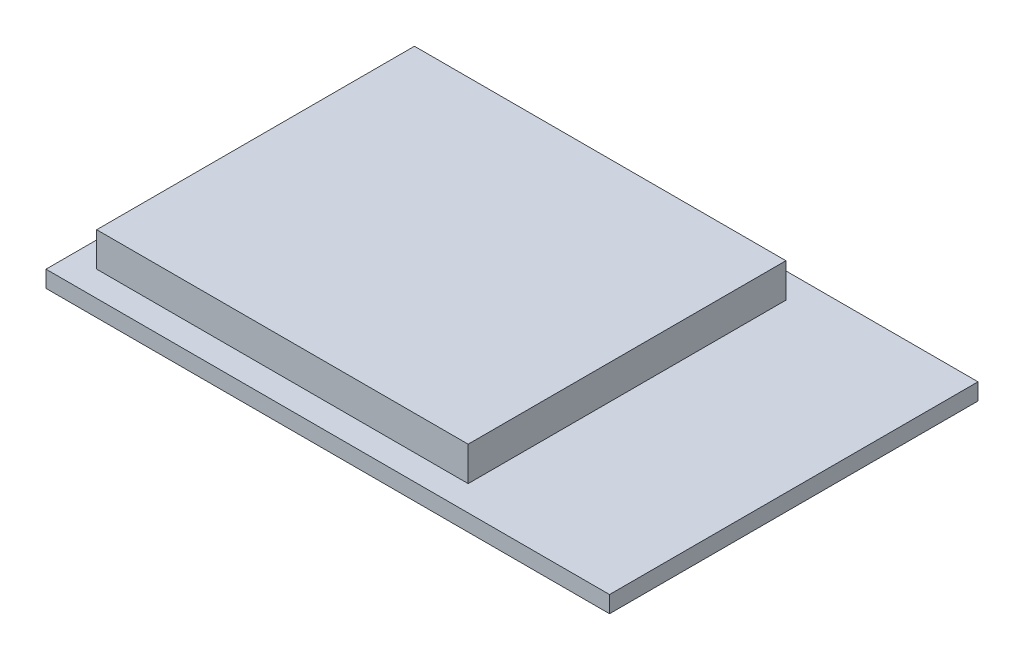
SolidWorks part; units mm, degrees
ref_plane "Ebene vorne" through (0, 0, 0) normal (0, 0, 1) x (1, 0, 0)
ref_plane "Ebene oben" through (0, 0, 0) normal (0, 1, 0) x (1, 0, 0)
ref_plane "Ebene rechts" through (0, 0, 0) normal (1, 0, 0) x (0, 0, -1)
sketch "Sketch1" plane through (0, 0, 0) normal (0, 1, 0) x (1, 0, 0)
  line L0 (-10.3687, 0) -> (25.2304, 0) construction
  line L2 (0, 11.05) -> (33.8, 11.05)
  line L3 (0, 11.05) -> (0, -11.05)
  line L4 (0, -11.05) -> (33.8, -11.05)
  line L5 (33.8, 11.05) -> (33.8, -11.05)
  dimension "D1" = 22.1
  dimension "D2" = 33.8
extrude "Boss-Extrude1" add sketch "Sketch1" along normal blind 1
sketch "Sketch2" plane through (0, 0, 0) normal (0, 1, 0) x (1, 0, 0)
  line L0 (0, 11.05) -> (0, -11.05) construction
  line L1 (23.8, 9.53) -> (1.52, 9.53)
  line L2 (23.8, 9.53) -> (23.8, -9.53)
  line L3 (23.8, -9.53) -> (1.52, -9.53)
  line L4 (1.52, 9.53) -> (1.52, -9.53)
  line L5 (0, -11.05) -> (33.8, -11.05) construction
  line L6 (33.8, 11.05) -> (0, 11.05) construction
  line L9 (33.8, -11.05) -> (33.8, 11.05) construction
  dimension "D1" = 1.52
  dimension "D2" = 1.52
  dimension "D3" = 1.52
  dimension "D4" = 10
extrude "Boss-Extrude2" [suppressed] add sketch "Sketch2" along normal blind 2 from offset 6 separate body
extrude "Boss-Extrude3" add sketch "Sketch2<2>" along normal blind 3.05
sketch "Sketch2<2>" plane through (0, 0, 0) normal (0, 1, 0) x (1, 0, 0) same geometry as "Sketch2"
